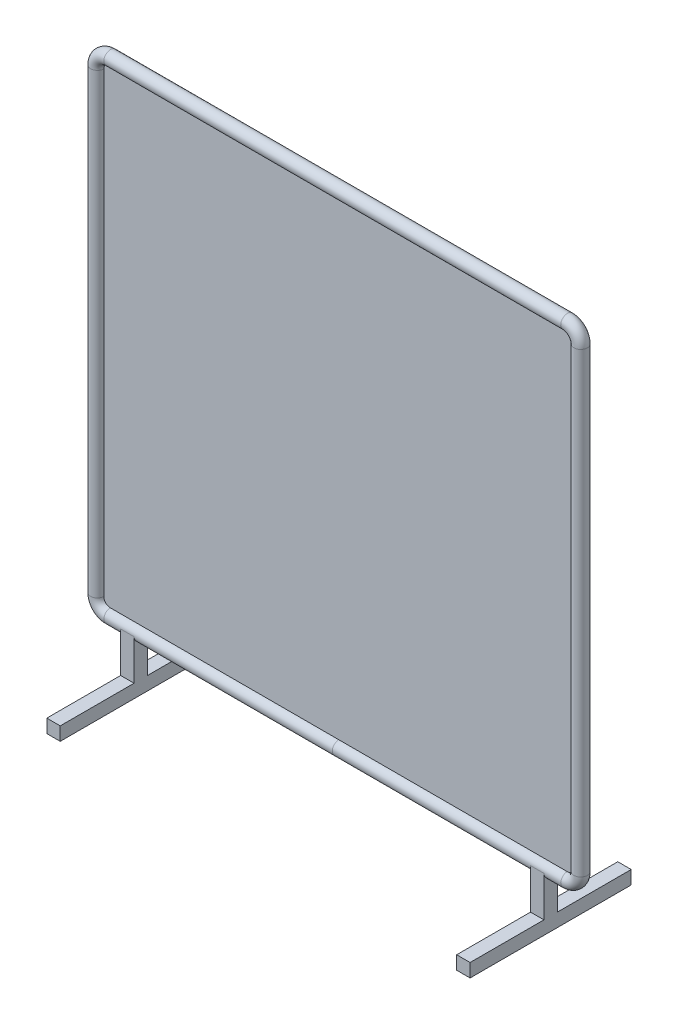
SolidWorks part; units mm, degrees
other "screen"
other "Frame"
ref_plane "Front Plane" through (0, 0, 0) normal (0, 0, 1) x (1, 0, 0)
ref_plane "Top Plane" through (0, 0, 0) normal (0, 1, 0) x (1, 0, 0)
ref_plane "Right Plane" through (0, 0, 0) normal (1, 0, 0) x (0, 0, -1)
sketch "Sketch1" plane through (0, 0, 0) normal (0, 0, 1) x (1, 0, 0)
  line L0 (0, -1000) -> (0, 49000) construction
  line L2 (-864.4, 1828.8) -> (864.4, 1828.8)
  line L3 (-914.4, 1778.8) -> (-914.4, 50)
  line L4 (-864.4, 0) -> (864.4, 0)
  line L5 (914.4, 1778.8) -> (914.4, 50)
  line L6 (0, 0) -> (0, 1828.8) construction
  line L7 (-914.4, 914.4) -> (914.4, 914.4) construction
  arc A0 (-914.4, 50) -> (-864.4, 0) centre (-864.4, 50) ccw
  arc A1 (864.4, 0) -> (914.4, 50) centre (864.4, 50) ccw
  arc A2 (864.4, 1828.8) -> (914.4, 1778.8) centre (864.4, 1778.8) cw
  arc A3 (-864.4, 1828.8) -> (-914.4, 1778.8) centre (-864.4, 1778.8) ccw
  point P1 (0, 914.4)
  point P7 (25.3606, 4.0793)
  point P10 (-914.4, 0)
  point P20 (914.4, 1828.8)
  point P23 (-914.4, 1828.8)
  dimension "D3" = 50
  dimension "D1" = 1828.8
  dimension "D2" = 1828.8
sketch "Sketch2" plane through (0, 0, 0) normal (1, 0, 0) x (0, 0, -1)
  circle A0 centre (0, 0) radius 25.4
  dimension "D1" = 50.8
sweep "Sweep1" add profiles "Sketch2" path "Sketch1"
sketch "Sketch3" plane through (0, 0, 0) normal (1, 0, 0) x (0, 0, -1)
  line L0 (0, -1000) -> (0, 49000) construction
  line L1 (-25.4, 0) -> (-25.4, -152.4)
  line L2 (-25.4, 50) -> (-25.4, 0) construction
  line L3 (-25.4, -152.4) -> (-304.8, -152.4)
  line L4 (-304.8, -152.4) -> (-304.8, -203.2)
  line L5 (25.4, 0) -> (25.4, -152.4)
  line L6 (25.4, -152.4) -> (304.8, -152.4)
  line L7 (304.8, -152.4) -> (304.8, -203.2)
  line L8 (-25.4, 0) -> (25.4, 0)
  line L9 (-304.8, -203.2) -> (304.8, -203.2)
  dimension "D1" = 50.8
  dimension "D2" = 203.2
  dimension "D3" = 609.6
extrude "Boss-Extrude1" add sketch "Sketch3" along normal blind 50.8 from offset 750
mirror "Mirror1" about plane through (0, 0, 0) normal (1, 0, 0) of "Boss-Extrude1"
extrude "Boss-Extrude2" add sketch "Sketch1<2>" along normal mid plane 2 separate body
sketch "Sketch1<2>" plane through (0, 0, 0) normal (0, 0, 1) x (1, 0, 0) same geometry as "Sketch1"
